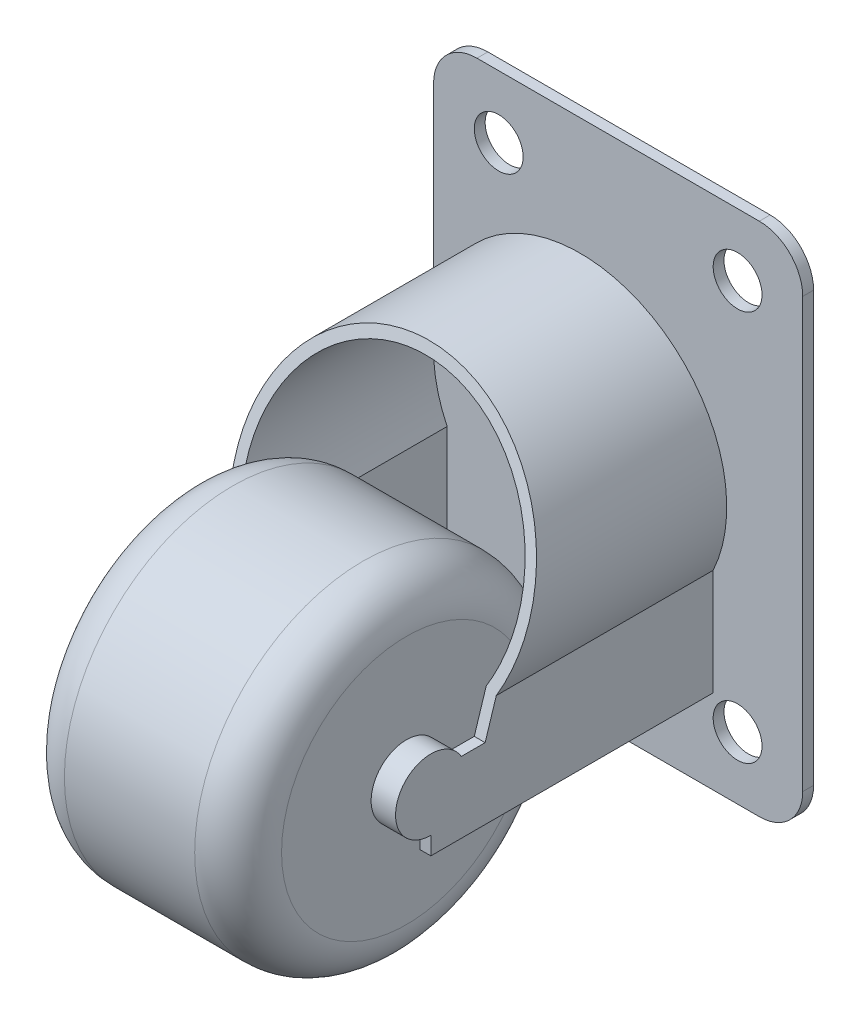
SolidWorks part; units mm, degrees
ref_plane "前视基准面" through (0, 0, 0) normal (0, 0, 1) x (1, 0, 0)
ref_plane "上视基准面" through (0, 0, 0) normal (0, 1, 0) x (1, 0, 0)
ref_plane "右视基准面" through (0, 0, 0) normal (1, 0, 0) x (0, 0, -1)
sketch "草图1" plane through (0, 0, 0) normal (0, 0, 1) x (1, 0, 0)
  line L0 (0, 0) -> (0, 20)
  line L1 (22.5, 30.8972) -> (22.5, 27.5869) construction
  line L2 (45, 0) -> (45, 20)
  line L3 (0, 0) -> (45, 0) construction
  arc A0 (0, 20) -> (45, 20) centre (22.5, 30.8972) cw
  point P7 (22.5, 55.8972)
  dimension "D1" = 25
  dimension "D2" = 45
  dimension "D3" = 20
extrude "拉伸-薄壁1" add sketch "草图1" along normal blind 50 thin thin type one direction wall 2
sketch "草图2" plane through (47, 0, 0) normal (1, 0, 0) x (0, 0, -1)
  line L0 (-17.5942, 83.8095) -> (-40, 13.0633)
  line L3 (-17.5942, 83.8095) -> (-17.5942, 95.1604)
  line L4 (-17.5942, 95.1604) -> (-58.1892, 95.1604)
  line L5 (-58.1892, 95.1604) -> (-46.8498, 13.0633)
  line L6 (-46.8498, 13.0633) -> (-40, 13.0633)
extrude "切除-拉伸1" cut sketch "草图2" against normal through all both and the other way through all
ref_plane "基准面1" through (22.5, 0, 0) normal (1, 0, 0) x (0, 0, -1)
sketch "草图3" plane through (22.5, 0, 0) normal (1, 0, 0) x (0, 0, -1)
  line L0 (-50, 0) -> (-50, 19.5504) construction
  circle A0 centre (-50, 9.7752) radius 31
  dimension "D1" = 62
extrude "凸台-拉伸1" add sketch "草图3" along normal blind 20 and the other way blind 20 separate body
fillet "圆角1" radius 8 2 edges at (2.5, 9.7752, 19) (42.5, 9.7752, 19)
sketch "草图4" plane through (47, 0, 0) normal (1, 0, 0) x (0, 0, -1)
  line L0 (-50, 0) -> (-50, 19.5504) construction
  circle A0 centre (-50, 9.7752) radius 6.5
  dimension "D1" = 13
extrude "凸台-拉伸2" add sketch "草图4" against normal up to surface (49 mm away) up to face at (-2, 13.041, 34.0676)
sketch "草图5" plane through (0, 0, 0) normal (0, 0, -1) x (-1, 0, 0)
  line L6 (2, 0) -> (2, 19.5504)
  line L7 (-47, 19.5504) -> (-47, 0)
  line L8 (-47, 0) -> (-45, 0)
  line L9 (-45, 0) -> (-45, 20)
  line L10 (0, 20) -> (0, 0)
  line L11 (0, 0) -> (2, 0)
  line L12 (2, 0) -> (2, 19.5504)
  line L13 (-47, 19.5504) -> (-47, 0)
  line L14 (-47, 0) -> (2, 0)
  arc A2 (2, 19.5504) -> (-47, 19.5504) centre (-22.5, 30.8972) ccw
  arc A3 (0, 20) -> (-45, 20) centre (-22.5, 30.8972) ccw
  arc A4 (2, 19.5504) -> (-47, 19.5504) centre (-22.5, 30.8972) ccw
  dimension "D1" = 0
extrude "凸台-拉伸3" add sketch "草图5" along normal blind 2
sketch "草图6" plane through (0, 0, -2) normal (0, 0, -1) x (-1, 0, 0)
  line L0 (-22.5, 57.8972) -> (-22.5, 0) construction
  line L1 (-47, 0) -> (2, 0) construction
  arc A0 (2, 19.5504) -> (-47, 19.5504) centre (-22.5, 30.8972) ccw construction
  circle A1 centre (-22.5, 25) radius 10
  dimension "D1" = 20
  dimension "D2" = 25
extrude "凸台-拉伸4" add sketch "草图6" along normal blind 7
sketch "草图7" plane through (0, 0, -9) normal (0, 0, -1) x (-1, 0, 0)
  line L1 (-56.5, -22.5) -> (11.5, -22.5)
  line L2 (-56.5, -22.5) -> (-56.5, 72.5)
  line L3 (-56.5, 72.5) -> (11.5, 72.5)
  line L4 (11.5, -22.5) -> (11.5, 72.5)
  line L5 (-56.5, -22.5) -> (11.5, 72.5) construction
  line L6 (-56.5, 72.5) -> (11.5, -22.5) construction
  point P0 (-22.5, 25)
  dimension "D1" = 95
  dimension "D2" = 68
extrude "凸台-拉伸5" add sketch "草图7" along normal blind 2
sketch "草图11" plane through (47, 0, 0) normal (1, 0, 0) x (0, 0, -1)
  line L0 (-56.4973, 9.5866) -> (-57.3744, 39.8055)
  line L1 (-57.3744, 39.8055) -> (-40.639, 39.8055)
  line L2 (-40.639, 39.8055) -> (-43.5, 9.7752)
  circle A0 centre (-50, 9.7752) radius 6.5
  line M2 (-40, 13.0633) -> (-44.393, 13.0633)
  arc M3 (-44.393, 13.0633) -> (-47.2063, 15.6442) centre (-50, 9.7752) ccw
  line M4 (-47.2063, 15.6442) -> (-47.7458, 19.5504)
  line M5 (-47.7458, 19.5504) -> (-50, 19.5504)
  line M6 (-50, 19.5504) -> (-50, 16.2752)
  arc M7 (-50, 16.2752) -> (-50, 3.2752) centre (-50, 9.7752) ccw
extrude "切除-拉伸2" cut sketch "草图11" against normal blind 2 and the other way blind 12 contours L2 L1 L0 M7 M6 M5 M4 M3 M2 | A0 M4 M5 M6 region at (47, 27.9618, 49.4319) region at (47, 17.7509, 48.7042)
mirror "镜向1" about plane through (22.5, 0, 0) normal (1, 0, 0) of "切除-拉伸2"
sketch "草图12" plane through (-2, 0, 0) normal (-1, 0, 0) x (0, 0, 1)
  circle A0 centre (50, 9.7752) radius 31 construction
  point P0 (81, 9.7752)
fillet "圆角2" radius 8 4 edges at (56.5, 72.5, -10) (-11.5, 72.5, -10) (56.5, -22.5, -10) (-11.5, -22.5, -10)
sketch "草图13" plane through (0, 0, -11) normal (0, 0, -1) x (-1, 0, 0)
  line L0 (-56.5, 25) -> (11.5, 25) construction
  line L1 (-56.5, 64.5) -> (-56.5, -14.5) construction
  line L2 (11.5, -14.5) -> (11.5, 64.5) construction
  line L4 (-44.5, -11) -> (-0.5, -11) construction
  line L5 (-44.5, -11) -> (-44.5, 61) construction
  line L6 (-44.5, 61) -> (-0.5, 61) construction
  line L7 (-0.5, -11) -> (-0.5, 61) construction
  line L8 (-44.5, -11) -> (-0.5, 61) construction
  line L9 (-44.5, 61) -> (-0.5, -11) construction
  circle A0 centre (-44.5, 61) radius 4.5
  circle A1 centre (-0.5, 61) radius 4.5
  circle A2 centre (-0.5, -11) radius 4.5
  circle A3 centre (-44.5, -11) radius 4.5
  point P6 (-22.5, 25)
  dimension "D3" = 9
  dimension "D1" = 44
  dimension "D2" = 72
extrude "切除-拉伸3" cut sketch "草图13" against normal blind 10
